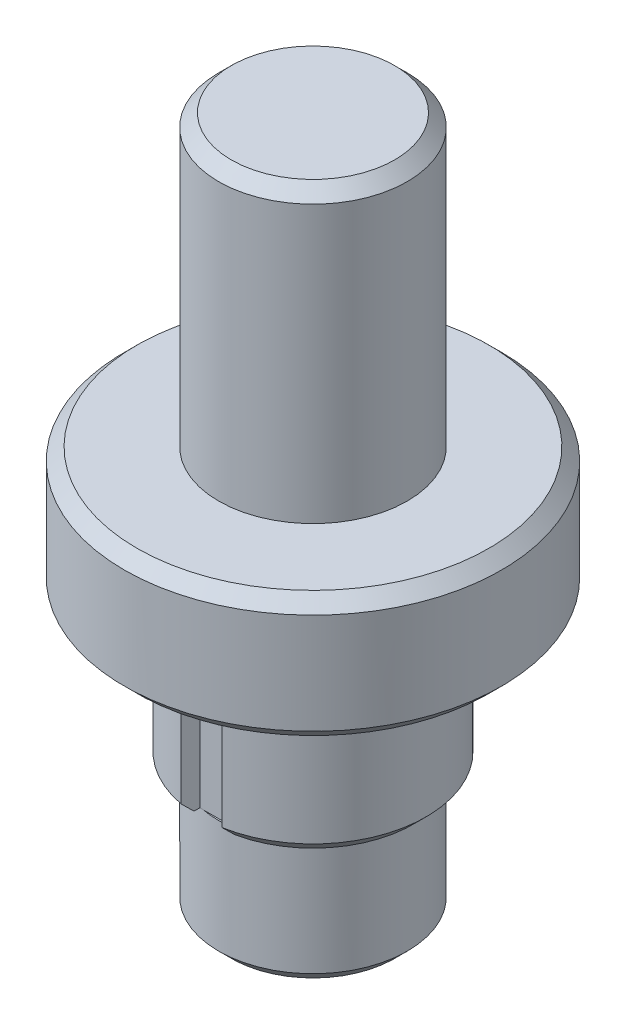
SolidWorks part; units mm, degrees
ref_plane "Front Plane" through (0, 0, 0) normal (0, 0, 1) x (1, 0, 0)
ref_plane "Top Plane" through (0, 0, 0) normal (0, 1, 0) x (1, 0, 0)
ref_plane "Right Plane" through (0, 0, 0) normal (1, 0, 0) x (0, 0, -1)
sketch "Sketch1" plane through (0, 0, 0) normal (0, 0, 1) x (1, 0, 0)
  line L0 (0, 0) -> (0, 55)
  line L1 (0, 55) -> (7.5, 55)
  line L3 (9, 10) -> (7.5, 10)
  line L4 (7.5, 10) -> (7.5, 0)
  line L5 (7.5, 0) -> (0, 0)
  line L6 (9, 10) -> (9, 22)
  line L7 (9, 22) -> (15, 22)
  line L8 (15, 22) -> (15, 32)
  line L9 (15, 32) -> (7.5, 32)
  line L10 (7.5, 32) -> (7.5, 55)
  dimension "D1" = 7.5
  dimension "D2" = 12
  dimension "D3" = 10
  dimension "D4" = 55
  dimension "D5" = 10
  dimension "D6" = 9
  dimension "D7" = 15
revolve "Revolve1" add sketch "Sketch1" angle 360 about L0
ref_axis "Axis1" through (0, 32, 0) along (0, -1, 0)
sketch "Sketch2" plane through (0, 10, 0) normal (0, -1, 0) x (1, 0, 0)
  line L1 (-1.625, 10.625) -> (1.625, 10.625)
  line L2 (-1.625, 10.625) -> (-1.625, 7.375)
  line L3 (-1.625, 7.375) -> (1.625, 7.375)
  line L4 (1.625, 10.625) -> (1.625, 7.375)
  line L5 (-1.625, 10.625) -> (1.625, 7.375) construction
  line L6 (-1.625, 7.375) -> (1.625, 10.625) construction
  circle A0 centre (0, 0) radius 9 construction
  point P0 (0, 9)
  dimension "D1" = 3.25
extrude "Cut-Extrude1" cut sketch "Sketch2" against normal up to surface (12 mm away) up to face at (0, 22, -15)
chamfer "Chamfer1" distance 1 angle 45 5 edges at (0, 55, -7.5) (0, 0, -7.5) (0, 10, -9) (0, 22, -15) (0, 32, -15)
